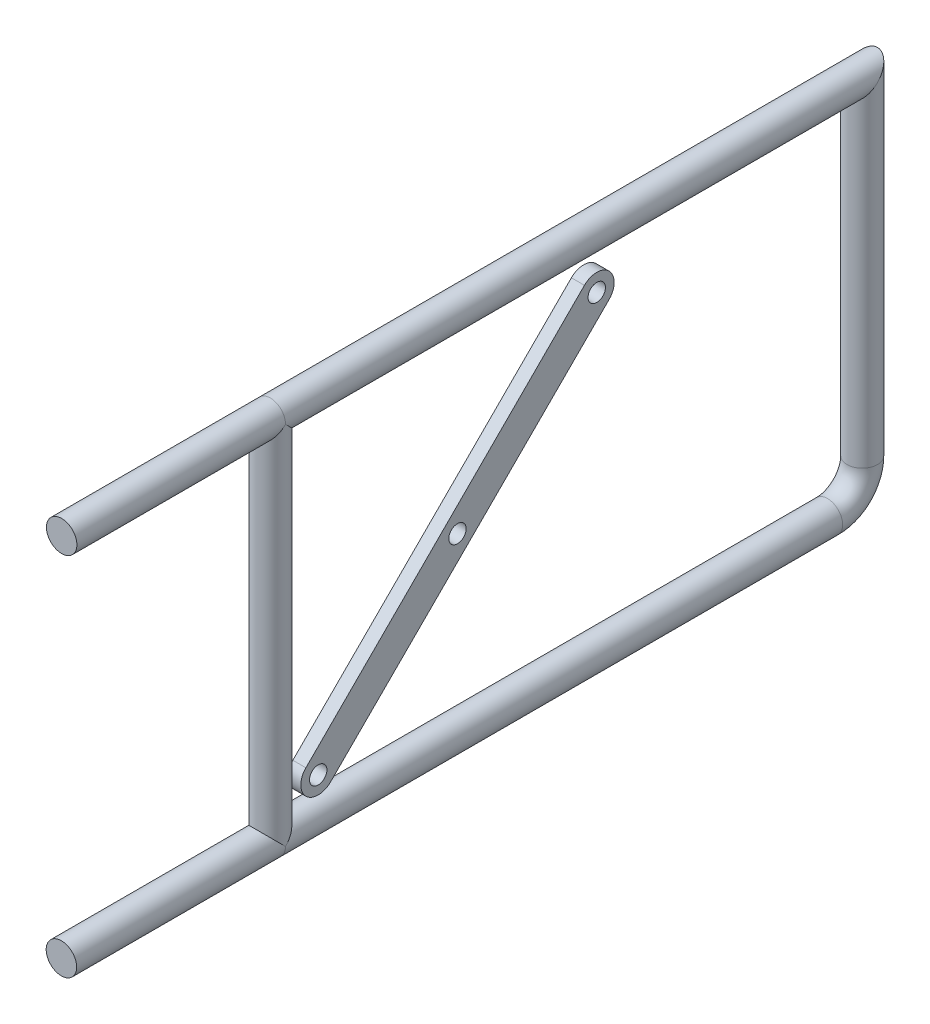
SolidWorks part; units mm, degrees
note: The reader was unsure of these and kept them because the rebuilt part matched: shared geometry of "Sketch3<8>", "Sketch1<23>".
ref_plane "Front Plane" through (0, 0, 0) normal (0, 0, 1) x (1, 0, 0)
ref_plane "Top Plane" through (0, 0, 0) normal (0, 1, 0) x (1, 0, 0)
ref_plane "Right Plane" through (0, 0, 0) normal (1, 0, 0) x (0, 0, -1)
sketch "Sketch1" plane through (0, 0, 0) normal (1, 0, 0) x (0, 0, -1)
  line L0 (126.1633, -30.1592) -> (152.2128, -152.4)
  line L2 (152.2128, -431.8) -> (584.0128, -431.8)
  line L4 (584.0128, -673.1) -> (584.0128, -431.8)
  line L5 (152.2128, -431.8) -> (0, -431.8)
  line L6 (558.6128, -698.5) -> (152.2128, -698.5)
  line L7 (88.9, 0) -> (0, 0)
  line L8 (152.2128, -152.4) -> (431.6128, -152.4)
  line L10 (457.0128, -177.8) -> (457.0128, -273.05)
  line L16 (457.0128, -273.05) -> (558.6128, -273.05)
  line L17 (584.0128, -298.45) -> (584.0128, -431.8)
  line L18 (-0.1872, -698.5) -> (152.2128, -698.5)
  line L19 (152.2128, -698.5) -> (152.2128, -431.8)
  line L20 (152.2128, -152.4) -> (152.2128, -431.8)
  arc A0 (88.9, 0) -> (126.1633, -30.1592) centre (88.9, -38.1) cw
  arc A1 (584.0128, -673.1) -> (558.6128, -698.5) centre (558.6128, -673.1) cw
  arc A2 (584.0128, -298.45) -> (558.6128, -273.05) centre (558.6128, -298.45) ccw
  arc A3 (431.6128, -152.4) -> (457.0128, -177.8) centre (431.6128, -177.8) cw
  point P5 (584.0128, -698.5)
  point P24 (584.0128, -273.05)
  point P30 (457.0128, -152.4)
  dimension "D2" = 38.1
  dimension "D11" = 25.4
  dimension "D9" = 25.4
  dimension "D1" = 88.9
  dimension "D3" = 120.65
  dimension "D4" = 431.8
  dimension "D5" = 431.8
  dimension "D6" = 279.4
  dimension "D7" = 152.4
  dimension "D8" = 546.1
  dimension "D10" = 127
  dimension "D17" = 124.9856
sketch "Sketch3" plane through (0, 0, 0) normal (0, 0, 1) x (1, 0, 0)
  circle A0 centre (0, -698.5) radius 11.1125
  dimension "D1" = 22.225
sweep "Sweep1" add profiles "Sketch3" path "Sketch1"
sweep "Sweep2" add profiles "Sketch3<8>" path "Sketch1<23>"
sketch "Sketch3<8>" plane through (0, 0, 0) normal (0, 0, 1) x (1, 0, 0) same geometry as "Sketch3"
sketch "Sketch1<23>" plane through (0, 0, 0) normal (1, 0, 0) x (0, 0, -1) same geometry as "Sketch1"
sketch "Sketch10" plane through (0, 0, 0) normal (1, 0, 0) x (0, 0, -1)
  line L1 (152.4, -914.4) -> (-272.7134, -914.4)
  line L2 (152.2128, -698.5) -> (152.2128, -431.8) construction
  circle A0 centre (152.2128, -609.6) radius 304.8
  dimension "D1" = 609.6
  dimension "D2" = 88.9
sketch "Sketch11" plane through (0, 0, 0) normal (1, 0, 0) x (0, 0, -1)
  line L0 (584.0128, -647.7) -> (152.2128, -647.7)
  line L1 (584.0128, -673.1) -> (584.0128, -431.8) construction
  line L2 (152.2128, -698.5) -> (152.2128, -431.8) construction
  line L3 (152.2128, -647.7) -> (152.2128, -698.5)
  line L4 (152.2128, -698.5) -> (558.6128, -698.5)
  line L5 (584.0128, -673.1) -> (584.0128, -647.7)
  line L6 (584.0128, -431.8) -> (584.0128, -482.6)
  line L7 (584.0128, -482.6) -> (152.2128, -482.6)
  line L8 (152.2128, -482.6) -> (152.2128, -431.8)
  line L9 (152.2128, -431.8) -> (584.0128, -431.8)
  line L10 (380.8128, -463.55) -> (177.6128, -666.75) construction
  line L11 (389.793, -472.5303) -> (186.593, -675.7303)
  line L12 (371.8325, -454.5697) -> (168.6325, -657.7697)
  line L13 (380.8128, -666.75) -> (177.6128, -463.55) construction
  line L14 (371.8325, -675.7303) -> (168.6325, -472.5303)
  line L15 (389.793, -657.7697) -> (186.593, -454.5697)
  line L16 (380.8128, -463.55) -> (507.8128, -463.55) construction
  line L17 (380.8128, -450.85) -> (507.8128, -450.85)
  line L18 (380.8128, -476.25) -> (507.8128, -476.25)
  line L19 (380.8128, -666.75) -> (507.8128, -666.75) construction
  line L20 (380.8128, -654.05) -> (507.8128, -654.05)
  line L21 (380.8128, -679.45) -> (507.8128, -679.45)
  line L22 (177.6128, -463.55) -> (177.6128, -666.75) construction
  line L23 (177.6128, -565.15) -> (446.4211, -666.75) construction
  line L24 (177.6128, -666.75) -> (446.4211, -565.15) construction
  line L25 (177.6128, -532.9233) -> (431.9175, -666.75) construction
  line L26 (431.9175, -666.75) -> (431.9175, -532.9233) construction
  line L27 (431.9175, -532.9233) -> (177.6128, -666.75) construction
  arc A0 (584.0128, -673.1) -> (558.6128, -698.5) centre (558.6128, -673.1) cw
  circle A1 centre (177.6128, -463.55) radius 6.35
  circle A2 centre (177.6128, -666.75) radius 6.35
  circle A3 centre (279.2128, -565.15) radius 6.35
  arc A4 (380.8128, -450.85) -> (380.8128, -476.25) centre (380.8128, -463.55) ccw
  arc A5 (389.793, -472.5303) -> (371.8325, -454.5697) centre (380.8128, -463.55) ccw
  arc A6 (168.6325, -657.7697) -> (186.593, -675.7303) centre (177.6128, -666.75) ccw
  arc A7 (371.8325, -675.7303) -> (389.793, -657.7697) centre (380.8128, -666.75) ccw
  arc A8 (186.593, -454.5697) -> (168.6325, -472.5303) centre (177.6128, -463.55) ccw
  arc A9 (507.8128, -476.25) -> (507.8128, -450.85) centre (507.8128, -463.55) ccw
  arc A10 (380.8128, -654.05) -> (380.8128, -679.45) centre (380.8128, -666.75) ccw
  arc A11 (507.8128, -679.45) -> (507.8128, -654.05) centre (507.8128, -666.75) ccw
  arc A12 (380.8128, -463.55) -> (464.982, -666.75) centre (177.6064, -666.7541) cw
  circle A13 centre (380.8128, -463.55) radius 6.35
  circle A14 centre (380.8128, -666.75) radius 6.35
  point P12 (584.0128, -698.5)
  point P27 (279.2128, -565.15)
  point P32 (279.2128, -565.15)
  point P39 (444.3128, -463.55)
  point P44 (444.3128, -666.75)
  dimension "D1" = 25.4
  dimension "D4" = 12.7
  dimension "D5" = 12.7
  dimension "D8" = 12.7
  dimension "D12" = 287.3756
  dimension "D2" = 50.8
  dimension "D3" = 50.8
  dimension "D6" = 19.05
  dimension "D7" = 19.05
  dimension "D9" = 90
  dimension "D10" = 25.4
  dimension "D11" = 76.2
extrude "Boss-Extrude1" add sketch "Sketch11" along normal blind 9.525 separate body contours L11 A6 L12 A5 | A13 | A3 | A2
